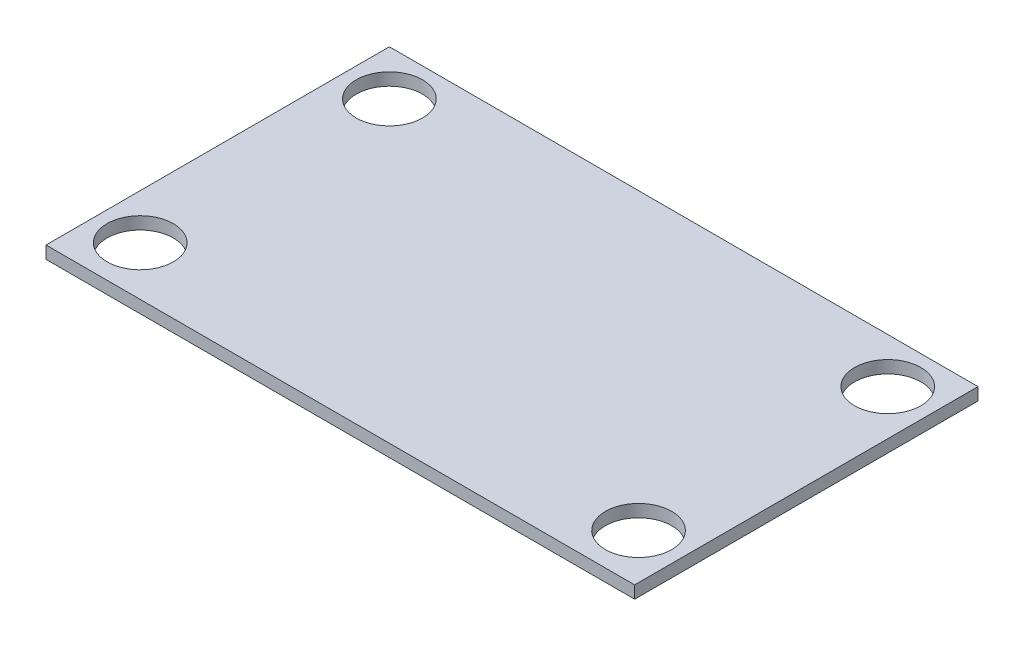
SolidWorks part; units mm, degrees
ref_plane "Front Plane" through (0, 0, 0) normal (0, 0, 1) x (1, 0, 0)
ref_plane "Top Plane" through (0, 0, 0) normal (0, 1, 0) x (1, 0, 0)
ref_plane "Right Plane" through (0, 0, 0) normal (1, 0, 0) x (0, 0, -1)
sketch "Sketch1" plane through (0, 0, 0) normal (0, 1, 0) x (1, 0, 0)
  line L0 (4.6, 30.4) -> (0, 30.4) construction
  line L1 (0, 0) -> (60, 0)
  line L2 (0, 0) -> (0, 35)
  line L3 (0, 35) -> (60, 35)
  line L4 (60, 0) -> (60, 35)
  line L5 (4.6, 30.4) -> (55.4, 30.4) construction
  line L6 (4.6, 30.4) -> (4.6, 5) construction
  line L7 (4.6, 5) -> (55.4, 5) construction
  line L8 (55.4, 30.4) -> (55.4, 5) construction
  line L9 (4.6, 30.4) -> (4.6, 35) construction
  circle A0 centre (4.6, 30.4) radius 3.3782
  circle A1 centre (55.4, 30.4) radius 3.3782
  circle A2 centre (4.6, 5) radius 3.3782
  circle A3 centre (55.4, 5) radius 3.3782
  point P13 (30, 30.4)
  point P14 (30, 35)
  dimension "D5" = 6.7564
  dimension "D1" = 60
  dimension "D2" = 35
  dimension "D3" = 50.8
  dimension "D4" = 25.4
extrude "Boss-Extrude1" add sketch "Sketch1" along normal blind 1.27
